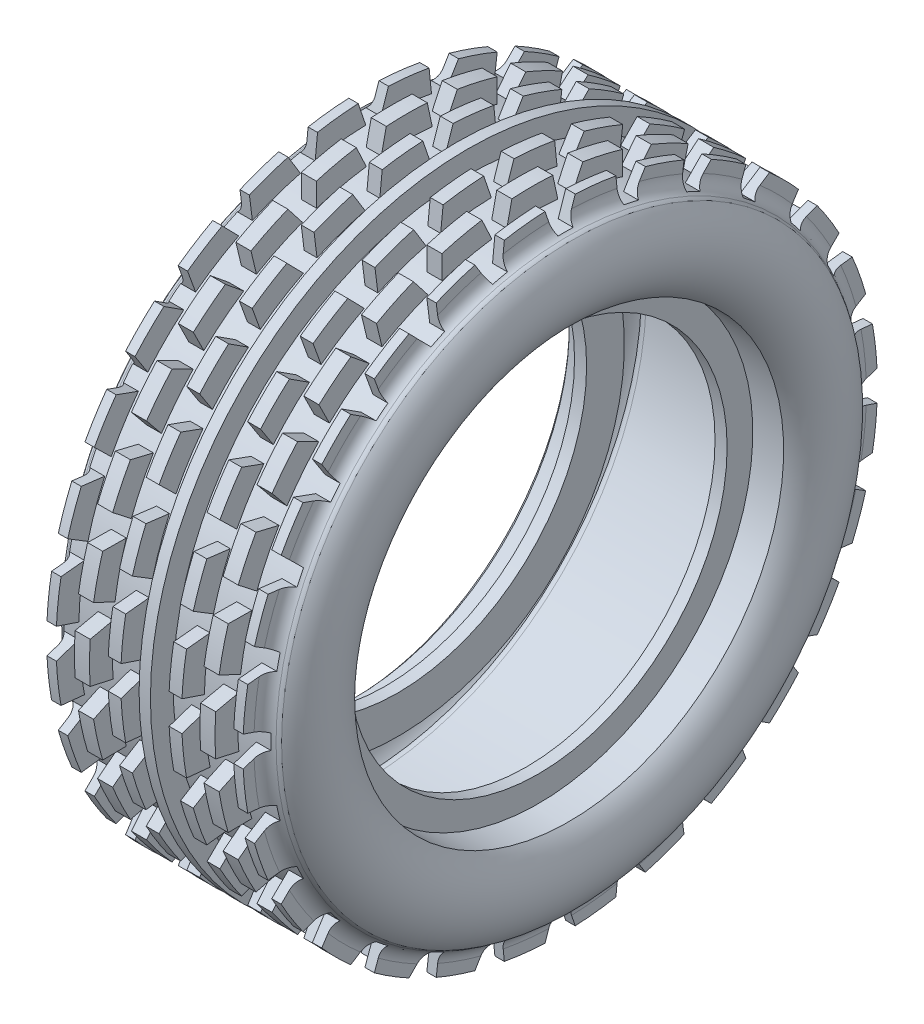
SolidWorks part; units mm, degrees
ref_plane "Front Plane" through (0, 0, 0) normal (0, 0, 1) x (1, 0, 0)
ref_plane "Top Plane" through (0, 0, 0) normal (0, 1, 0) x (1, 0, 0)
ref_plane "Right Plane" through (0, 0, 0) normal (1, 0, 0) x (0, 0, -1)
sketch "Sketch1" plane through (0, 0, 0) normal (0, 0, 1) x (1, 0, 0)
  line L0 (-8.3108, 0) -> (8.3108, 0) construction
  line L8 (0, 48.3703) -> (0, 3.5626) construction
  line L16 (12.99, 37.4) -> (0, 37.4)
  line L19 (12.99, 40.5425) -> (12.99, 42)
  line L20 (13.0099, 30) -> (8.5, 30)
  line L21 (8.5, 30) -> (8.5, 25)
  line L22 (12.99, 42) -> (11.74, 42)
  line L23 (11.74, 42) -> (11.74, 39)
  line L24 (11.74, 39) -> (9.31, 39)
  line L25 (9.31, 39) -> (9.31, 42)
  line L26 (9.31, 42) -> (7.31, 42)
  line L27 (7.31, 42) -> (7.31, 39)
  line L28 (12.99, 39) -> (0, 39) construction
  line L29 (7.31, 39) -> (4.88, 39)
  line L30 (4.88, 39) -> (4.88, 42)
  line L31 (4.88, 42) -> (3.18, 42)
  line L32 (3.18, 42) -> (3.18, 39)
  line L33 (3.18, 39) -> (0.75, 39)
  line L34 (0.75, 39) -> (0.75, 42)
  line L35 (0.75, 42) -> (0, 42)
  line L36 (13.5, 30) -> (8.5, 30) construction
  line L37 (8.5, 30.1776) -> (9.3651, 30.0926) construction
  line L38 (10.1, 28.2456) -> (10.1, 28.2456) construction
  line L39 (10.1, 28.2456) -> (10.1, 25.5) construction
  line L40 (8.5, 30.1776) -> (8.5, 25.5) construction
  line L41 (14.1843, 28.4) -> (10.1, 28.4)
  line L42 (10.1, 28.4) -> (10.1, 25)
  line L43 (8.5, 25) -> (10.1, 25)
  line L44 (0, 42) -> (0, 37.4)
  line L45 (12.99, 39) -> (0, 39) construction
  arc A4 (13.5, 37.2602) -> (13.8303, 30.4282) centre (9.2359, 33.6301) cw
  arc A5 (14.1204, 38.7414) -> (14.5739, 38.4619) centre (12.99, 36.4) cw
  arc A6 (13.5, 37.2602) -> (13.5, 30) centre (9.2359, 33.6301) cw construction
  arc A7 (14.5739, 38.4619) -> (14.1843, 28.4) centre (9.2359, 33.6301) cw
  arc A8 (12.99, 37.4) -> (13.5, 37.2602) centre (12.99, 36.4) cw
  arc A9 (13.8303, 30.4282) -> (13.0099, 30) centre (13.0099, 31) cw
  arc A10 (12.99, 39) -> (14.5739, 38.4619) centre (12.99, 36.4) cw construction
  arc A11 (14.1204, 38.7414) -> (12.99, 40.5425) centre (14.99, 40.5425) cw
  arc A12 (10.5375, 29.9095) -> (9.3651, 30.0926) centre (10.1323, 31.1597) cw construction
  arc A13 (10.8491, 28.335) -> (10.1, 28.2456) centre (10.1323, 31.1597) cw construction
  arc A14 (13.5, 37.2602) -> (10.5375, 29.9095) centre (10.0764, 34.3676) cw construction
  arc A15 (14.5739, 38.4619) -> (10.8491, 28.335) centre (10.0764, 34.3676) cw construction
  arc A16 (12.99, 39) -> (14.5739, 38.4619) centre (12.99, 36.4) cw construction
  point P4 (0, 0)
  point P58 (13.5, 30)
  dimension "D7" = 5
  dimension "D9" = 1.7
  dimension "D12" = 42
  dimension "D13" = 17
  dimension "D3" = 5.6
  dimension "D4" = 5
  dimension "D5" = 0.75
  dimension "D6" = 3
  dimension "D8" = 1
  dimension "D15" = 2
  dimension "D18" = 1
  dimension "D2" = 1.6
  dimension "D10" = 2
  dimension "D11" = 1.25
  dimension "D14" = 1.6
  dimension "D16" = 2.43
  dimension "D17" = 8.5
revolve "Revolve3" add sketch "Sketch1" angle 360 about L0 region at (6.495, 37.6365, 0)
sketch "Sketch3" plane through (11.74, 0, 0) normal (-1, 0, 0) x (0, 0, 1)
  line L0 (-2, 41.9524) -> (-1, 38.9872)
  line L1 (2, 41.9524) -> (1, 38.9872)
  line L2 (7.3854, 41.3456) -> (7.7005, 38.2322)
  line L3 (11.2851, 40.4555) -> (9.6504, 37.7872)
  line L4 (16.4005, 38.6655) -> (16.0149, 35.5601)
  line L5 (20.0044, 36.93) -> (17.8169, 34.6923)
  line L6 (24.5932, 34.0467) -> (23.5263, 31.1049)
  line L7 (27.7205, 31.5527) -> (25.0899, 29.8579)
  line L8 (31.5527, 27.7205) -> (29.8579, 25.0899)
  line L9 (34.0467, 24.5932) -> (31.1049, 23.5263)
  line L10 (36.93, 20.0044) -> (34.6923, 17.8169)
  line L11 (38.6655, 16.4005) -> (35.5601, 16.0149)
  line L12 (40.4555, 11.2851) -> (37.7872, 9.6504)
  line L13 (41.3456, 7.3854) -> (38.2322, 7.7005)
  line L14 (41.9524, 2) -> (38.9872, 1)
  line L15 (41.9524, -2) -> (38.9872, -1)
  line L16 (41.3456, -7.3854) -> (38.2322, -7.7005)
  line L17 (40.4555, -11.2851) -> (37.7872, -9.6504)
  line L18 (38.6655, -16.4005) -> (35.5601, -16.0149)
  line L19 (36.93, -20.0044) -> (34.6923, -17.8169)
  line L20 (34.0467, -24.5932) -> (31.1049, -23.5263)
  line L21 (31.5527, -27.7205) -> (29.8579, -25.0899)
  line L22 (27.7205, -31.5527) -> (25.0899, -29.8579)
  line L23 (24.5932, -34.0467) -> (23.5263, -31.1049)
  line L24 (20.0044, -36.93) -> (17.8169, -34.6923)
  line L25 (16.4005, -38.6655) -> (16.0149, -35.5601)
  line L26 (11.2851, -40.4555) -> (9.6504, -37.7872)
  line L27 (7.3854, -41.3456) -> (7.7005, -38.2322)
  line L28 (2, -41.9524) -> (1, -38.9872)
  line L29 (-2, -41.9524) -> (-1, -38.9872)
  line L30 (-7.3854, -41.3456) -> (-7.7005, -38.2322)
  line L31 (-11.2851, -40.4555) -> (-9.6504, -37.7872)
  line L32 (-16.4005, -38.6655) -> (-16.0149, -35.5601)
  line L33 (-20.0044, -36.93) -> (-17.8169, -34.6923)
  line L34 (-24.5932, -34.0467) -> (-23.5263, -31.1049)
  line L35 (-27.7205, -31.5527) -> (-25.0899, -29.8579)
  line L36 (-31.5527, -27.7205) -> (-29.8579, -25.0899)
  line L37 (-34.0467, -24.5932) -> (-31.1049, -23.5263)
  line L38 (-36.93, -20.0044) -> (-34.6923, -17.8169)
  line L39 (-38.6655, -16.4005) -> (-35.5601, -16.0149)
  line L40 (-40.4555, -11.2851) -> (-37.7872, -9.6504)
  line L41 (-41.3456, -7.3854) -> (-38.2322, -7.7005)
  line L42 (-41.9524, -2) -> (-38.9872, -1)
  line L43 (-41.9524, 2) -> (-38.9872, 1)
  line L44 (-41.3456, 7.3854) -> (-38.2322, 7.7005)
  line L45 (-40.4555, 11.2851) -> (-37.7872, 9.6504)
  line L46 (-38.6655, 16.4005) -> (-35.5601, 16.0149)
  line L47 (-36.93, 20.0044) -> (-34.6923, 17.8169)
  line L48 (-34.0467, 24.5932) -> (-31.1049, 23.5263)
  line L49 (-31.5527, 27.7205) -> (-29.8579, 25.0899)
  line L50 (-27.7205, 31.5527) -> (-25.0899, 29.8579)
  line L51 (-24.5932, 34.0467) -> (-23.5263, 31.1049)
  line L52 (-20.0044, 36.93) -> (-17.8169, 34.6923)
  line L53 (-16.4005, 38.6655) -> (-16.0149, 35.5601)
  line L54 (-11.2851, 40.4555) -> (-9.6504, 37.7872)
  line L55 (-7.3854, 41.3456) -> (-7.7005, 38.2322)
  circle A0 centre (0, 0) radius 39 construction
  arc A1 (1, 38.9872) -> (-1, 38.9872) centre (0, 0) ccw
  circle A2 centre (0, 0) radius 42 construction
  arc A4 (-2, 41.9524) -> (2, 41.9524) centre (0, 36.022) cw
  arc A5 (9.6504, 37.7872) -> (7.7005, 38.2322) centre (0, 0) ccw
  arc A6 (7.3854, 41.3456) -> (11.2851, 40.4555) centre (8.0156, 35.1189) cw
  arc A7 (17.8169, 34.6923) -> (16.0149, 35.5601) centre (0, 0) ccw
  arc A8 (16.4005, 38.6655) -> (20.0044, 36.93) centre (15.6294, 32.4547) cw
  arc A9 (25.0899, 29.8579) -> (23.5263, 31.1049) centre (0, 0) ccw
  arc A10 (24.5932, 34.0467) -> (27.7205, 31.5527) centre (22.4594, 28.1631) cw
  arc A11 (31.1049, 23.5263) -> (29.8579, 25.0899) centre (0, 0) ccw
  arc A12 (31.5527, 27.7205) -> (34.0467, 24.5932) centre (28.1631, 22.4594) cw
  arc A13 (35.5601, 16.0149) -> (34.6923, 17.8169) centre (0, 0) ccw
  arc A14 (36.93, 20.0044) -> (38.6655, 16.4005) centre (32.4547, 15.6294) cw
  arc A15 (38.2322, 7.7005) -> (37.7872, 9.6504) centre (0, 0) ccw
  arc A16 (40.4555, 11.2851) -> (41.3456, 7.3854) centre (35.1189, 8.0156) cw
  arc A17 (38.9872, -1) -> (38.9872, 1) centre (0, 0) ccw
  arc A18 (41.9524, 2) -> (41.9524, -2) centre (36.022, 0) cw
  arc A19 (37.7872, -9.6504) -> (38.2322, -7.7005) centre (0, 0) ccw
  arc A20 (41.3456, -7.3854) -> (40.4555, -11.2851) centre (35.1189, -8.0156) cw
  arc A21 (34.6923, -17.8169) -> (35.5601, -16.0149) centre (0, 0) ccw
  arc A22 (38.6655, -16.4005) -> (36.93, -20.0044) centre (32.4547, -15.6294) cw
  arc A23 (29.8579, -25.0899) -> (31.1049, -23.5263) centre (0, 0) ccw
  arc A24 (34.0467, -24.5932) -> (31.5527, -27.7205) centre (28.1631, -22.4594) cw
  arc A25 (23.5263, -31.1049) -> (25.0899, -29.8579) centre (0, 0) ccw
  arc A26 (27.7205, -31.5527) -> (24.5932, -34.0467) centre (22.4594, -28.1631) cw
  arc A27 (16.0149, -35.5601) -> (17.8169, -34.6923) centre (0, 0) ccw
  arc A28 (20.0044, -36.93) -> (16.4005, -38.6655) centre (15.6294, -32.4547) cw
  arc A29 (7.7005, -38.2322) -> (9.6504, -37.7872) centre (0, 0) ccw
  arc A30 (11.2851, -40.4555) -> (7.3854, -41.3456) centre (8.0156, -35.1189) cw
  arc A31 (-1, -38.9872) -> (1, -38.9872) centre (0, 0) ccw
  arc A32 (2, -41.9524) -> (-2, -41.9524) centre (0, -36.022) cw
  arc A33 (-9.6504, -37.7872) -> (-7.7005, -38.2322) centre (0, 0) ccw
  arc A34 (-7.3854, -41.3456) -> (-11.2851, -40.4555) centre (-8.0156, -35.1189) cw
  arc A35 (-17.8169, -34.6923) -> (-16.0149, -35.5601) centre (0, 0) ccw
  arc A36 (-16.4005, -38.6655) -> (-20.0044, -36.93) centre (-15.6294, -32.4547) cw
  arc A37 (-25.0899, -29.8579) -> (-23.5263, -31.1049) centre (0, 0) ccw
  arc A38 (-24.5932, -34.0467) -> (-27.7205, -31.5527) centre (-22.4594, -28.1631) cw
  arc A39 (-31.1049, -23.5263) -> (-29.8579, -25.0899) centre (0, 0) ccw
  arc A40 (-31.5527, -27.7205) -> (-34.0467, -24.5932) centre (-28.1631, -22.4594) cw
  arc A41 (-35.5601, -16.0149) -> (-34.6923, -17.8169) centre (0, 0) ccw
  arc A42 (-36.93, -20.0044) -> (-38.6655, -16.4005) centre (-32.4547, -15.6294) cw
  arc A43 (-38.2322, -7.7005) -> (-37.7872, -9.6504) centre (0, 0) ccw
  arc A44 (-40.4555, -11.2851) -> (-41.3456, -7.3854) centre (-35.1189, -8.0156) cw
  arc A45 (-38.9872, 1) -> (-38.9872, -1) centre (0, 0) ccw
  arc A46 (-41.9524, -2) -> (-41.9524, 2) centre (-36.022, 0) cw
  arc A47 (-37.7872, 9.6504) -> (-38.2322, 7.7005) centre (0, 0) ccw
  arc A48 (-41.3456, 7.3854) -> (-40.4555, 11.2851) centre (-35.1189, 8.0156) cw
  arc A49 (-34.6923, 17.8169) -> (-35.5601, 16.0149) centre (0, 0) ccw
  arc A50 (-38.6655, 16.4005) -> (-36.93, 20.0044) centre (-32.4547, 15.6294) cw
  arc A51 (-29.8579, 25.0899) -> (-31.1049, 23.5263) centre (0, 0) ccw
  arc A52 (-34.0467, 24.5932) -> (-31.5527, 27.7205) centre (-28.1631, 22.4594) cw
  arc A53 (-23.5263, 31.1049) -> (-25.0899, 29.8579) centre (0, 0) ccw
  arc A54 (-27.7205, 31.5527) -> (-24.5932, 34.0467) centre (-22.4594, 28.1631) cw
  arc A55 (-16.0149, 35.5601) -> (-17.8169, 34.6923) centre (0, 0) ccw
  arc A56 (-20.0044, 36.93) -> (-16.4005, 38.6655) centre (-15.6294, 32.4547) cw
  arc A57 (-7.7005, 38.2322) -> (-9.6504, 37.7872) centre (0, 0) ccw
  arc A58 (-11.2851, 40.4555) -> (-7.3854, 41.3456) centre (-8.0156, 35.1189) cw
  point P147 (0, 0)
  dimension "D1" = 4
  dimension "D2" = 2
  dimension "D3" = 1
  dimension "D4" = 1
  dimension "D5" = 28
extrude "Cut-Extrude1" cut sketch "Sketch3" against normal blind 10
extrude "Cut-Extrude2" cut sketch "Sketch3<2>" along normal blind 4 from offset 5
sketch "Sketch3<2>" plane through (11.74, 0, 0) normal (-1, 0, 0) x (0, 0, 1) same geometry as "Sketch3"
sketch "Sketch4" plane through (9.31, 0, 0) normal (1, 0, 0) x (0, 0, -1)
  line L4 (-4.3666, 38.7548) -> (-5.4712, 48.558) construction
  line L6 (-5.3589, 38.6301) -> (-6.6846, 41.4646)
  line L7 (-3.3715, 38.854) -> (-2.7097, 41.9125)
  line L8 (3.3715, 38.854) -> (2.7097, 41.9125)
  line L9 (5.3589, 38.6301) -> (6.6846, 41.4646)
  line L10 (11.9328, 37.1296) -> (11.9682, 40.2587)
  line L11 (13.8205, 36.4691) -> (15.7438, 38.9376)
  line L12 (19.8957, 33.5434) -> (20.6265, 36.5861)
  line L13 (21.5892, 32.4794) -> (24.0134, 34.458)
  line L14 (26.861, 28.2752) -> (28.2506, 31.079)
  line L15 (28.2752, 26.861) -> (31.079, 28.2506)
  line L16 (32.4794, 21.5892) -> (34.458, 24.0134)
  line L17 (33.5434, 19.8957) -> (36.5861, 20.6265)
  line L18 (36.4691, 13.8205) -> (38.9376, 15.7438)
  line L19 (37.1296, 11.9328) -> (40.2587, 11.9682)
  line L20 (38.6301, 5.3589) -> (41.4646, 6.6846)
  line L21 (38.854, 3.3715) -> (41.9125, 2.7097)
  line L22 (38.854, -3.3715) -> (41.9125, -2.7097)
  line L23 (38.6301, -5.3589) -> (41.4646, -6.6846)
  line L24 (37.1296, -11.9328) -> (40.2587, -11.9682)
  line L25 (36.4691, -13.8205) -> (38.9376, -15.7438)
  line L26 (33.5434, -19.8957) -> (36.5861, -20.6265)
  line L27 (32.4794, -21.5892) -> (34.458, -24.0134)
  line L28 (28.2752, -26.861) -> (31.079, -28.2506)
  line L29 (26.861, -28.2752) -> (28.2506, -31.079)
  line L30 (21.5892, -32.4794) -> (24.0134, -34.458)
  line L31 (19.8957, -33.5434) -> (20.6265, -36.5861)
  line L32 (13.8205, -36.4691) -> (15.7438, -38.9376)
  line L33 (11.9328, -37.1296) -> (11.9682, -40.2587)
  line L34 (5.3589, -38.6301) -> (6.6846, -41.4646)
  line L35 (3.3715, -38.854) -> (2.7097, -41.9125)
  line L36 (-3.3715, -38.854) -> (-2.7097, -41.9125)
  line L37 (-5.3589, -38.6301) -> (-6.6846, -41.4646)
  line L38 (-11.9328, -37.1296) -> (-11.9682, -40.2587)
  line L39 (-13.8205, -36.4691) -> (-15.7438, -38.9376)
  line L40 (-19.8957, -33.5434) -> (-20.6265, -36.5861)
  line L41 (-21.5892, -32.4794) -> (-24.0134, -34.458)
  line L42 (-26.861, -28.2752) -> (-28.2506, -31.079)
  line L43 (-28.2752, -26.861) -> (-31.079, -28.2506)
  line L44 (-32.4794, -21.5892) -> (-34.458, -24.0134)
  line L45 (-33.5434, -19.8957) -> (-36.5861, -20.6265)
  line L46 (-36.4691, -13.8205) -> (-38.9376, -15.7438)
  line L47 (-37.1296, -11.9328) -> (-40.2587, -11.9682)
  line L48 (-38.6301, -5.3589) -> (-41.4646, -6.6846)
  line L49 (-38.854, -3.3715) -> (-41.9125, -2.7097)
  line L50 (-38.854, 3.3715) -> (-41.9125, 2.7097)
  line L51 (-38.6301, 5.3589) -> (-41.4646, 6.6846)
  line L52 (-37.1296, 11.9328) -> (-40.2587, 11.9682)
  line L53 (-36.4691, 13.8205) -> (-38.9376, 15.7438)
  line L54 (-33.5434, 19.8957) -> (-36.5861, 20.6265)
  line L55 (-32.4794, 21.5892) -> (-34.458, 24.0134)
  line L56 (-28.2752, 26.861) -> (-31.079, 28.2506)
  line L57 (-26.861, 28.2752) -> (-28.2506, 31.079)
  line L58 (-21.5892, 32.4794) -> (-24.0134, 34.458)
  line L59 (-19.8957, 33.5434) -> (-20.6265, 36.5861)
  line L60 (-13.8205, 36.4691) -> (-15.7438, 38.9376)
  line L61 (-11.9328, 37.1296) -> (-11.9682, 40.2587)
  arc A0 (-6.6846, 41.4646) -> (-2.7097, 41.9125) centre (-4.0332, 35.7955) cw
  arc A3 (2.7097, 41.9125) -> (6.6846, 41.4646) centre (4.0332, 35.7955) cw
  arc A6 (-3.3715, 38.854) -> (-5.3589, 38.6301) centre (0, 0) ccw
  circle A7 centre (0, 0) radius 39 construction
  arc A8 (5.3589, 38.6301) -> (3.3715, 38.854) centre (0, 0) ccw
  arc A11 (-2, 41.9524) -> (-7.3854, 41.3456) centre (0, 0) ccw construction
  arc A12 (11.9682, 40.2587) -> (15.7438, 38.9376) centre (11.8973, 34.0006) cw
  arc A13 (13.8205, 36.4691) -> (11.9328, 37.1296) centre (0, 0) ccw
  arc A14 (20.6265, 36.5861) -> (24.0134, 34.458) centre (19.1649, 30.5007) cw
  arc A15 (21.5892, 32.4794) -> (19.8957, 33.5434) centre (0, 0) ccw
  arc A16 (28.2506, 31.079) -> (31.079, 28.2506) centre (25.4714, 25.4714) cw
  arc A17 (28.2752, 26.861) -> (26.861, 28.2752) centre (0, 0) ccw
  arc A18 (34.458, 24.0134) -> (36.5861, 20.6265) centre (30.5007, 19.1649) cw
  arc A19 (33.5434, 19.8957) -> (32.4794, 21.5892) centre (0, 0) ccw
  arc A20 (38.9376, 15.7438) -> (40.2587, 11.9682) centre (34.0006, 11.8973) cw
  arc A21 (37.1296, 11.9328) -> (36.4691, 13.8205) centre (0, 0) ccw
  arc A22 (41.4646, 6.6846) -> (41.9125, 2.7097) centre (35.7955, 4.0332) cw
  arc A23 (38.854, 3.3715) -> (38.6301, 5.3589) centre (0, 0) ccw
  arc A24 (41.9125, -2.7097) -> (41.4646, -6.6846) centre (35.7955, -4.0332) cw
  arc A25 (38.6301, -5.3589) -> (38.854, -3.3715) centre (0, 0) ccw
  arc A26 (40.2587, -11.9682) -> (38.9376, -15.7438) centre (34.0006, -11.8973) cw
  arc A27 (36.4691, -13.8205) -> (37.1296, -11.9328) centre (0, 0) ccw
  arc A28 (36.5861, -20.6265) -> (34.458, -24.0134) centre (30.5007, -19.1649) cw
  arc A29 (32.4794, -21.5892) -> (33.5434, -19.8957) centre (0, 0) ccw
  arc A30 (31.079, -28.2506) -> (28.2506, -31.079) centre (25.4714, -25.4714) cw
  arc A31 (26.861, -28.2752) -> (28.2752, -26.861) centre (0, 0) ccw
  arc A32 (24.0134, -34.458) -> (20.6265, -36.5861) centre (19.1649, -30.5007) cw
  arc A33 (19.8957, -33.5434) -> (21.5892, -32.4794) centre (0, 0) ccw
  arc A34 (15.7438, -38.9376) -> (11.9682, -40.2587) centre (11.8973, -34.0006) cw
  arc A35 (11.9328, -37.1296) -> (13.8205, -36.4691) centre (0, 0) ccw
  arc A36 (6.6846, -41.4646) -> (2.7097, -41.9125) centre (4.0332, -35.7955) cw
  arc A37 (3.3715, -38.854) -> (5.3589, -38.6301) centre (0, 0) ccw
  arc A38 (-2.7097, -41.9125) -> (-6.6846, -41.4646) centre (-4.0332, -35.7955) cw
  arc A39 (-5.3589, -38.6301) -> (-3.3715, -38.854) centre (0, 0) ccw
  arc A40 (-11.9682, -40.2587) -> (-15.7438, -38.9376) centre (-11.8973, -34.0006) cw
  arc A41 (-13.8205, -36.4691) -> (-11.9328, -37.1296) centre (0, 0) ccw
  arc A42 (-20.6265, -36.5861) -> (-24.0134, -34.458) centre (-19.1649, -30.5007) cw
  arc A43 (-21.5892, -32.4794) -> (-19.8957, -33.5434) centre (0, 0) ccw
  arc A44 (-28.2506, -31.079) -> (-31.079, -28.2506) centre (-25.4714, -25.4714) cw
  arc A45 (-28.2752, -26.861) -> (-26.861, -28.2752) centre (0, 0) ccw
  arc A46 (-34.458, -24.0134) -> (-36.5861, -20.6265) centre (-30.5007, -19.1649) cw
  arc A47 (-33.5434, -19.8957) -> (-32.4794, -21.5892) centre (0, 0) ccw
  arc A48 (-38.9376, -15.7438) -> (-40.2587, -11.9682) centre (-34.0006, -11.8973) cw
  arc A49 (-37.1296, -11.9328) -> (-36.4691, -13.8205) centre (0, 0) ccw
  arc A50 (-41.4646, -6.6846) -> (-41.9125, -2.7097) centre (-35.7955, -4.0332) cw
  arc A51 (-38.854, -3.3715) -> (-38.6301, -5.3589) centre (0, 0) ccw
  arc A52 (-41.9125, 2.7097) -> (-41.4646, 6.6846) centre (-35.7955, 4.0332) cw
  arc A53 (-38.6301, 5.3589) -> (-38.854, 3.3715) centre (0, 0) ccw
  arc A54 (-40.2587, 11.9682) -> (-38.9376, 15.7438) centre (-34.0006, 11.8973) cw
  arc A55 (-36.4691, 13.8205) -> (-37.1296, 11.9328) centre (0, 0) ccw
  arc A56 (-36.5861, 20.6265) -> (-34.458, 24.0134) centre (-30.5007, 19.1649) cw
  arc A57 (-32.4794, 21.5892) -> (-33.5434, 19.8957) centre (0, 0) ccw
  arc A58 (-31.079, 28.2506) -> (-28.2506, 31.079) centre (-25.4714, 25.4714) cw
  arc A59 (-26.861, 28.2752) -> (-28.2752, 26.861) centre (0, 0) ccw
  arc A60 (-24.0134, 34.458) -> (-20.6265, 36.5861) centre (-19.1649, 30.5007) cw
  arc A61 (-19.8957, 33.5434) -> (-21.5892, 32.4794) centre (0, 0) ccw
  arc A62 (-15.7438, 38.9376) -> (-11.9682, 40.2587) centre (-11.8973, 34.0006) cw
  arc A63 (-11.9328, 37.1296) -> (-13.8205, 36.4691) centre (0, 0) ccw
  point P3 (-4.3666, 38.7548)
  point P152 (0, 0)
  dimension "D1" = 1
  dimension "D2" = 2
  dimension "D3" = 28
extrude "Cut-Extrude3" cut sketch "Sketch4" against normal blind 4
mirror "Mirror1" about plane through (0, 0, 0) normal (1, 0, 0) of bodies 104
